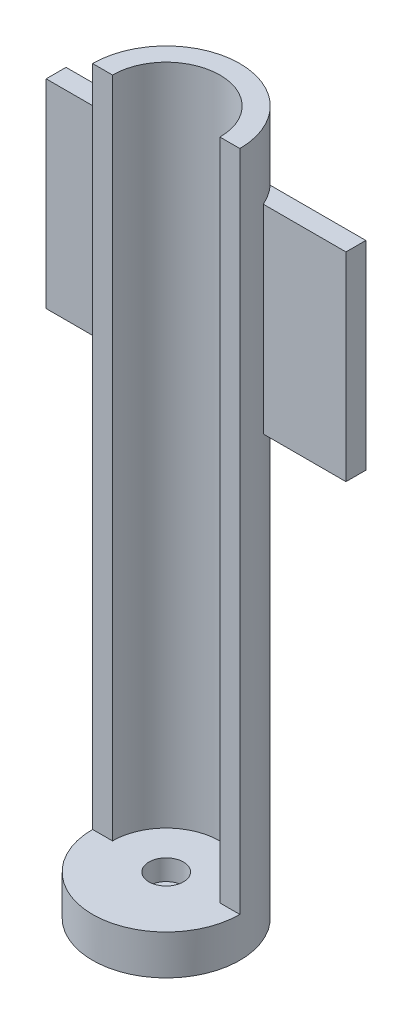
SolidWorks part; units mm, degrees
ref_plane "Front Plane" through (0, 0, 0) normal (0, 0, 1) x (1, 0, 0)
ref_plane "Top Plane" through (0, 0, 0) normal (0, 1, 0) x (1, 0, 0)
ref_plane "Right Plane" through (0, 0, 0) normal (1, 0, 0) x (0, 0, -1)
sketch "Sketch1" plane through (0, 0, 0) normal (0, 1, 0) x (1, 0, 0)
  circle A0 centre (0, 0) radius 8.1
  circle A1 centre (0, 0) radius 11.1
  dimension "D1" = 3
  dimension "D2" = 16.2
extrude "Boss-Extrude1" add sketch "Sketch1" along normal mid plane 100
sketch "Sketch2" plane through (0, -50, 0) normal (0, -1, 0) x (1, 0, 0)
  circle A0 centre (0, 0) radius 11.1
sketch "Sketch3" plane through (0, 0, 0) normal (0, 0, 1) x (1, 0, 0)
  line L1 (-101.5851, -102.8012) -> (101.5851, -102.8012)
  line L2 (-101.5851, -102.8012) -> (-101.5851, 102.8012)
  line L3 (-101.5851, 102.8012) -> (101.5851, 102.8012)
  line L4 (101.5851, -102.8012) -> (101.5851, 102.8012)
  line L5 (-101.5851, -102.8012) -> (101.5851, 102.8012) construction
  line L6 (-101.5851, 102.8012) -> (101.5851, -102.8012) construction
  point P0 (0, 0)
extrude "Cut-Extrude1" cut sketch "Sketch3" along normal through all
sketch "Sketch4" plane through (0, -50, 0) normal (0, -1, 0) x (1, 0, 0)
  circle A0 centre (0, 0) radius 11.1
extrude "Boss-Extrude3" add sketch "Sketch4" along normal blind 6
sketch "Sketch5" plane through (0, -50, 0) normal (0, 1, 0) x (1, 0, 0)
  circle A0 centre (0, 0) radius 2.6
  dimension "D1" = 5.2
extrude "Cut-Extrude2" cut sketch "Sketch5" against normal blind 3.1
ref_plane "Plane2" through (0, 0, -6) normal (0, 0, 1) x (1, 0, 0)
sketch "Sketch6" plane through (0, 0, -6) normal (0, 0, 1) x (1, 0, 0)
  line L0 (0, 17.3633) -> (0, 69.1455) construction
  line L1 (11.1, 50) -> (8.1, 50) construction
  line L2 (7.6, 40) -> (22.6, 40)
  line L3 (7.6, 40) -> (7.6, 10)
  line L4 (7.6, 10) -> (22.6, 10)
  line L5 (22.6, 40) -> (22.6, 10)
  line L7 (-22.6, 40) -> (-22.6, 10)
  line L8 (-7.6, 10) -> (-22.6, 10)
  line L9 (-7.6, 40) -> (-7.6, 10)
  line L10 (-7.6, 40) -> (-22.6, 40)
  dimension "D1" = 10
  dimension "D2" = 30
  dimension "D3" = 7.6
  dimension "D4" = 15
extrude "Boss-Extrude4" add sketch "Sketch6" along normal mid plane 3
sketch "Sketch7" plane through (0, 0, -7.5) normal (0, 0, -1) x (-1, 0, 0)
  line L0 (15.3915, 40) -> (15.3915, 10) construction
  line L1 (8.1829, 40) -> (22.6, 40) construction
  line L2 (22.6, 10) -> (8.1829, 10) construction
  line L3 (0, 0) -> (0, 47.416) construction
  text T0 "A2N\r\n3mm mold" font "Century Gothic" height in points 11
extrude "Boss-Extrude5" add sketch "Sketch7" along normal blind 1.5
